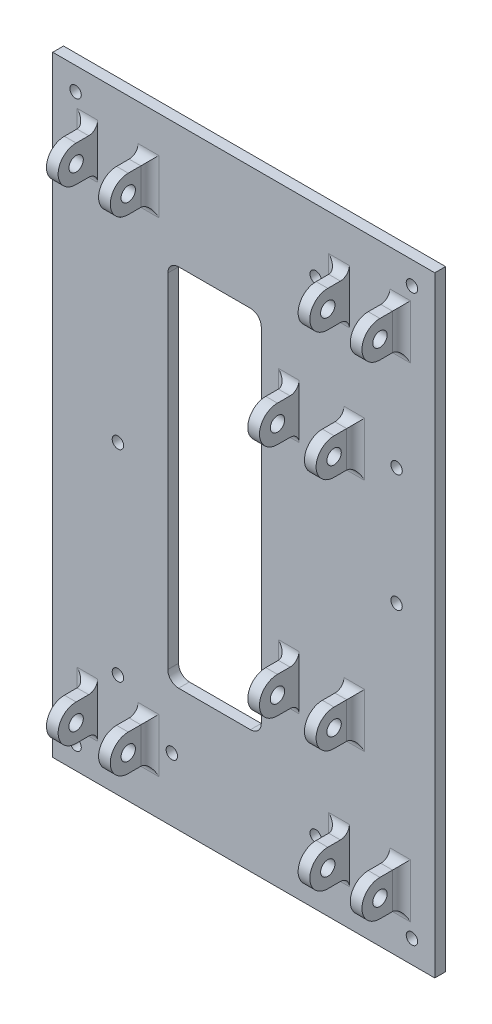
SolidWorks part; units mm, degrees
other "Markup3"
sketch "Sketch7" plane through (228.6, -342.9, 31.75) normal (0.076, -0.0024, 0.9971) x (0.9961, 0.0458, -0.0758)
other "Markup4"
sketch "Sketch8" plane through (228.6, -342.9, 31.75) normal (0.076, -0.0024, 0.9971) x (0.9961, 0.0458, -0.0758)
material "7075-T6 (SN)"
ref_plane "Front Plane" through (0, 0, 0) normal (0, 0, 1) x (1, 0, 0)
ref_plane "Top Plane" through (0, 0, 0) normal (0, 1, 0) x (1, 0, 0)
ref_plane "Right Plane" through (0, 0, 0) normal (1, 0, 0) x (0, 0, -1)
sketch "Sketch1" plane through (0, 0, 0) normal (0, 0, 1) x (1, 0, 0)
  line L1 (0, 0) -> (212.5, 0)
  line L2 (0, 0) -> (0, -339.725)
  line L3 (0, -339.725) -> (212.5, -339.725)
  line L4 (212.5, 0) -> (212.5, -339.725)
  dimension "D1" = 339.725
  dimension "D2" = 212.5
extrude "Boss-Extrude1" add sketch "Sketch1" along normal blind 6
sketch "Sketch2" plane through (0, 0, 6) normal (0, 0, 1) x (1, 0, 0)
  line L0 (0, 0) -> (0, -339.725) construction
  line L1 (25, -25.2425) -> (47.5, -25.2425) construction
  line L2 (25, -25.2425) -> (25, -45.2425)
  line L3 (25, -45.2425) -> (47.5, -45.2425) construction
  line L4 (47.5, -25.2425) -> (47.5, -45.2425)
  line L5 (165, -25.2425) -> (187.5, -25.2425) construction
  line L6 (165, -25.2425) -> (165, -45.2425)
  line L7 (165, -45.2425) -> (187.5, -45.2425) construction
  line L8 (187.5, -25.2425) -> (187.5, -45.2425)
  line L18 (137, -114.5325) -> (137, -225.1925) construction
  line L19 (0, -169.8625) -> (106.25, -169.8625) construction
  line L20 (54, -35.2425) -> (158.5, -35.2425) construction
  line L26 (165, -25.2425) -> (158.5, -25.2425)
  line L27 (165, -25.2425) -> (165, -45.2425)
  line L28 (165, -45.2425) -> (158.5, -45.2425)
  line L29 (158.5, -25.2425) -> (158.5, -45.2425)
  line L30 (187.5, -25.2425) -> (194, -25.2425)
  line L31 (187.5, -25.2425) -> (187.5, -45.2425)
  line L32 (187.5, -45.2425) -> (194, -45.2425)
  line L33 (194, -25.2425) -> (194, -45.2425)
  line L34 (47.5, -25.2425) -> (54, -25.2425)
  line L35 (47.5, -25.2425) -> (47.5, -45.2425)
  line L36 (47.5, -45.2425) -> (54, -45.2425)
  line L37 (54, -25.2425) -> (54, -45.2425)
  line L38 (25, -25.2425) -> (18.5, -25.2425)
  line L39 (25, -25.2425) -> (25, -45.2425)
  line L40 (25, -45.2425) -> (18.5, -45.2425)
  line L41 (18.5, -25.2425) -> (18.5, -45.2425)
  line L65 (212.5, -339.725) -> (212.5, 0) construction
  line L66 (137, -225.1925) -> (162, -225.1925) construction
  line L67 (158.5, -304.4825) -> (194, -304.4825) construction
  line L68 (149.5, -104.5325) -> (149.5, -235.1925) construction
  line L76 (18.5, -35.2425) -> (54, -35.2425) construction
  line L77 (18.5, -304.4825) -> (54, -304.4825) construction
  line L78 (36.25, -35.2425) -> (36.25, -304.4825) construction
  line L79 (137, -94.5325) -> (162, -94.5325) construction
  line L80 (54, -304.4825) -> (158.5, -304.4825) construction
  line L81 (106.25, -35.2425) -> (106.25, -304.4825) construction
  line L82 (106.25, -169.8625) -> (212.5, -169.8625) construction
  line L83 (130.5, -94.5325) -> (130.5, -114.5325)
  line L84 (137, -114.5325) -> (130.5, -114.5325)
  line L86 (137, -94.5325) -> (130.5, -94.5325)
  line L88 (137, -94.5325) -> (137, -114.5325)
  line L89 (162, -114.5325) -> (168.5, -114.5325)
  line L90 (162, -114.5325) -> (162, -94.5325)
  line L91 (168.5, -94.5325) -> (168.5, -114.5325)
  line L92 (162, -94.5325) -> (168.5, -94.5325)
  line L93 (130.5, -235.1925) -> (168.5, -235.1925) construction
  line L96 (137, -245.1925) -> (162, -245.1925) construction
  line L97 (162, -245.1925) -> (168.5, -245.1925)
  line L98 (168.5, -245.1925) -> (168.5, -225.1925)
  line L103 (130.5, -104.5325) -> (168.5, -104.5325) construction
  line L104 (137, -114.5325) -> (162, -114.5325) construction
  line L106 (158.5, -35.2425) -> (194, -35.2425) construction
  line L108 (176.25, -35.2425) -> (176.25, -304.4825) construction
  line L109 (165, -294.4825) -> (187.5, -294.4825) construction
  line L112 (165, -314.4825) -> (187.5, -314.4825) construction
  line L113 (25, -294.4825) -> (47.5, -294.4825) construction
  line L114 (25, -314.4825) -> (47.5, -314.4825) construction
  line L117 (162, -114.5325) -> (162, -225.1925) construction
  line L118 (18.5, -314.4825) -> (18.5, -294.4825)
  line L119 (25, -294.4825) -> (18.5, -294.4825)
  line L120 (25, -314.4825) -> (25, -294.4825)
  line L121 (25, -314.4825) -> (18.5, -314.4825)
  line L122 (54, -314.4825) -> (54, -294.4825)
  line L123 (47.5, -294.4825) -> (54, -294.4825)
  line L124 (47.5, -314.4825) -> (47.5, -294.4825)
  line L125 (47.5, -314.4825) -> (54, -314.4825)
  line L126 (194, -314.4825) -> (194, -294.4825)
  line L127 (187.5, -294.4825) -> (194, -294.4825)
  line L128 (187.5, -314.4825) -> (187.5, -294.4825)
  line L129 (187.5, -314.4825) -> (194, -314.4825)
  line L130 (158.5, -314.4825) -> (158.5, -294.4825)
  line L131 (165, -294.4825) -> (158.5, -294.4825)
  line L132 (165, -314.4825) -> (165, -294.4825)
  line L133 (165, -314.4825) -> (158.5, -314.4825)
  line L134 (187.5, -314.4825) -> (187.5, -294.4825)
  line L135 (165, -314.4825) -> (165, -294.4825)
  line L136 (47.5, -314.4825) -> (47.5, -294.4825)
  line L137 (25, -314.4825) -> (25, -294.4825)
  line L138 (162, -225.1925) -> (162, -245.1925)
  line L139 (162, -225.1925) -> (168.5, -225.1925)
  line L140 (137, -245.1925) -> (137, -225.1925)
  line L141 (137, -245.1925) -> (130.5, -245.1925)
  line L142 (137, -225.1925) -> (130.5, -225.1925)
  line L143 (130.5, -245.1925) -> (130.5, -225.1925)
  point P63 (194, -35.2425)
  point P101 (212.5, -169.8625)
  point P103 (158.5, -35.2425)
  dimension "D5" = 43.25
  dimension "D1" = 20
  dimension "D2" = 22.5
  dimension "D3" = 6.5
  dimension "D4" = 199.95
  dimension "D6" = 134.62
  dimension "D7" = 134.62
  dimension "D8" = 25
  dimension "D9" = 70
  dimension "D10" = 25
extrude "Boss-Extrude2" add sketch "Sketch2" along normal blind 24 contours L133 L132 L131 L130 | L128 L129 L126 L127 | L139 L138 L97 L98 | L143 L141 L140 L142 | L124 L125 L122 L123 | L121 L120 L119 L118 | L92 L90 L89 L91 | L88 L86 L83 L84 | L33 L30 L8 L32 | L37 L34 L4 L36 | L38 L41 L40 L2 | L26 L29 L28 L27 region at (21.75, -35.2425, 6) region at (50.75, -35.2425, 6) region at (190.75, -35.2425, 6) region at (133.75, -104.5325, 6) region at (165.25, -104.5325, 6) region at (165.25, -235.1925, 6) region at (21.75, -304.4825, 6) region at (50.75, -304.4825, 6) region at (190.75, -304.4825, 6) region at (161.75, -304.4825, 6) region at (133.75, -235.1925, 6)
sketch "Sketch3" plane through (18.5, 0, 0) normal (-1, 0, 0) x (0, 0, 1)
  line L0 (18, -104.5325) -> (6, -104.5325) construction
  line L1 (18, -304.4825) -> (6, -304.4825) construction
  line L2 (22, -235.1925) -> (37.7332, -235.1925) construction
  line L3 (22, -235.1925) -> (6, -235.1925) construction
  line L4 (18, -35.2425) -> (6, -35.2425) construction
  line L5 (6, -25.2425) -> (6, -45.2425) construction
  line L6 (6, -245.1925) -> (6, -225.1925) construction
  line L7 (6, 0) -> (6, -339.725) construction
  line L9 (18, -25.2425) -> (18, -12.9829)
  line L10 (18, -12.9829) -> (51.9495, -12.9829)
  line L11 (6, -245.1925) -> (6, -225.1925) construction
  line L12 (51.9495, -12.9829) -> (51.9495, -57.481)
  line L13 (51.9495, -57.481) -> (18, -57.481)
  line L14 (18, -57.481) -> (18, -45.2425)
  line L15 (52.4423, -132.3991) -> (18, -132.3991)
  line L16 (18, -94.5325) -> (18, -71.5915)
  line L17 (18, -71.5915) -> (52.4423, -71.5915)
  line L18 (18, -132.3991) -> (18, -114.5325)
  line L19 (52.4423, -71.5915) -> (52.4423, -132.3991)
  line L20 (52.5995, -270.3754) -> (18, -270.3754)
  line L21 (18, -225.1925) -> (18, -207.3064)
  line L22 (18, -207.3064) -> (52.5995, -207.3064)
  line L23 (18, -270.3754) -> (18, -245.1925)
  line L24 (52.5995, -207.3064) -> (52.5995, -270.3754)
  line L25 (52.621, -326.7211) -> (18, -326.7211)
  line L26 (18, -294.4825) -> (18, -282.2228)
  line L27 (18, -282.2228) -> (52.621, -282.2228)
  line L28 (18, -326.7211) -> (18, -314.4825)
  line L29 (52.621, -282.2228) -> (52.621, -326.7211)
  line L30 (6, -94.5325) -> (6, -114.5325) construction
  line L31 (30, -25.2425) -> (6, -25.2425) construction
  line L32 (30, -94.5325) -> (6, -94.5325) construction
  line L35 (6, -314.4825) -> (6, -294.4825) construction
  line L36 (6, -314.4825) -> (6, -294.4825) construction
  line L37 (18, -35.2425) -> (18, -104.5325) construction
  line L38 (18, -104.5325) -> (18, -235.1925) construction
  line L39 (18, -235.1925) -> (18, -304.4825) construction
  line L41 (30, -225.1925) -> (6, -225.1925) construction
  circle A0 centre (18, -35.2425) radius 4
  circle A1 centre (18, -235.1925) radius 4
  circle A2 centre (18, -35.2425) radius 5.5 construction
  circle A3 centre (18, -304.4825) radius 4
  circle A4 centre (18, -104.5325) radius 4
  arc A5 (18, -45.2425) -> (18, -25.2425) centre (18, -35.2425) ccw
  arc A6 (18, -114.5325) -> (18, -94.5325) centre (18, -104.5325) ccw
  arc A7 (18, -245.1925) -> (18, -225.1925) centre (18, -235.1925) ccw
  arc A8 (18, -314.4825) -> (18, -294.4825) centre (18, -304.4825) ccw
  point P62 (6, -304.4825)
  point P67 (6, -235.1925)
  dimension "D1" = 8
  dimension "D2" = 8
  dimension "D4" = 11
  dimension "D3" = 12
extrude "Cut-Extrude1" cut sketch "Sketch3" against normal through all both and the other way through all
fillet "Fillet2" radius 5 36 edges at (158.5, -304.4825, 6) (18.5, -304.4825, 6) (21.75, -45.2425, 6) (18.5, -35.2425, 6) (21.75, -25.2425, 6) (50.75, -25.2425, 6) (50.75, -45.2425, 6) (54, -35.2425, 6) (161.75, -25.2425, 6) (190.75, -25.2425, 6) (194, -35.2425, 6) (190.75, -45.2425, 6) (161.75, -45.2425, 6) (158.5, -35.2425, 6) (168.5, -104.5325, 6) (165.25, -114.5325, 6) (133.75, -114.5325, 6) (130.5, -104.5325, 6) (165.25, -94.5325, 6) (133.75, -94.5325, 6) (21.75, -294.4825, 6) (50.75, -294.4825, 6) (54, -304.4825, 6) (194, -304.4825, 6) (161.75, -294.4825, 6) (190.75, -294.4825, 6) (190.75, -314.4825, 6) (161.75, -314.4825, 6) (50.75, -314.4825, 6) (21.75, -314.4825, 6) (165.25, -225.1925, 6) (133.75, -225.1925, 6) (130.5, -235.1925, 6) (133.75, -245.1925, 6) (165.25, -245.1925, 6) (168.5, -235.1925, 6)
sketch "Sketch5" plane through (0, 0, 6) normal (0, 0, 1) x (1, 0, 0)
  line L0 (212.5, 0) -> (0, 0) construction
  line L1 (0, 0) -> (0, -339.725) construction
  line L2 (212.5, -339.725) -> (212.5, 0) construction
  line L5 (0, -169.8625) -> (212.5, -169.8625) construction
  line L6 (153.5, -35.2425) -> (59, -35.2425) construction
  line L7 (59, -20.2425) -> (59, -50.2425) construction
  line L8 (191.25, -104.5325) -> (191.25, -169.8625) construction
  line L9 (13.5, -50.2425) -> (59, -50.2425) construction
  line L10 (25, -50.2425) -> (13.5, -50.2425) construction
  line L11 (36.25, -50.2425) -> (36.25, -169.8625) construction
  line L15 (173.5, -89.5325) -> (173.5, -119.5325) construction
  line L16 (106.25, 0) -> (106.25, -339.725) construction
  line L17 (173.5, -104.5325) -> (191.25, -104.5325) construction
  line L26 (0, -339.725) -> (212.5, -339.725) construction
  circle A0 centre (12.7, -12.7) radius 3.175
  circle A1 centre (199.8, -12.7) radius 3.175
  circle A2 centre (66.25, -35.2425) radius 3.175
  circle A3 centre (146.25, -35.2425) radius 3.175
  circle A4 centre (176.25, -57.8625) radius 3.175
  circle A5 centre (36.25, -57.8625) radius 3.175
  circle A6 centre (191.25, -104.5325) radius 3.175
  circle A7 centre (36.25, -169.8625) radius 3.175
  circle A8 centre (191.25, -169.8625) radius 3.175
  circle A9 centre (36.25, -281.8625) radius 3.175
  circle A10 centre (66.25, -304.4825) radius 3.175
  circle A11 centre (12.7, -327.025) radius 3.175
  circle A12 centre (199.8, -327.025) radius 3.175
  circle A13 centre (146.25, -304.4825) radius 3.175
  circle A15 centre (191.25, -235.1925) radius 3.175
  dimension "D1" = 93.55
  dimension "D3" = 40
  dimension "D5" = 85
  dimension "D8" = 6.35
  dimension "D2" = 157.1625
  dimension "D4" = 112
extrude "Cut-Extrude2" cut sketch "Sketch5" against normal through all contours A0 | A5 | A3 | A1 | A4 | A6 | A7 | A8 | A12 | A13 | A10 | A9 | A11 region at (12.7, -12.7, 6) region at (199.8, -12.7, 6) region at (146.25, -35.2425, 6) region at (176.25, -57.8625, 6) region at (36.25, -57.8625, 6) region at (191.25, -104.5325, 6) region at (36.25, -169.8625, 6) region at (191.25, -169.8625, 6) region at (36.25, -281.8625, 6) region at (66.25, -304.4825, 6) region at (12.7, -327.025, 6) region at (199.8, -327.025, 6) region at (146.25, -304.4825, 6)
sketch "Sketch9" plane through (0, 0, 6) normal (0, 0, 1) x (1, 0, 0)
  line L0 (0, -169.8625) -> (212.5, -169.8625) construction
  line L11 (0, 0) -> (0, -339.725) construction
  line L12 (212.5, -339.725) -> (212.5, 0) construction
  line L14 (70, -271.3625) -> (110, -271.3625)
  line L15 (64, -265.3625) -> (64, -74.3625)
  line L16 (70, -68.3625) -> (110, -68.3625)
  line L17 (116, -265.3625) -> (116, -74.3625)
  line L18 (64, -271.3625) -> (116, -68.3625) construction
  line L19 (64, -68.3625) -> (116, -271.3625) construction
  arc A0 (110, -271.3625) -> (116, -265.3625) centre (110, -265.3625) ccw
  arc A1 (70, -271.3625) -> (64, -265.3625) centre (70, -265.3625) cw
  arc A2 (64, -74.3625) -> (70, -68.3625) centre (70, -74.3625) cw
  arc A5 (110, -68.3625) -> (116, -74.3625) centre (110, -74.3625) cw
  point P6 (90, -169.8625)
  point P22 (169.7848, -178.533)
  point P23 (214.9568, -251.8775)
  point P24 (158.9712, -185.193)
  point P25 (204.1432, -258.5375)
  dimension "D1" = 90
  dimension "D3" = 52
  dimension "D4" = 6
  dimension "D2" = 203
extrude "Cut-Extrude3" cut sketch "Sketch9" against normal through all contours L15 A2 L16 A5 L17 A0 L14 A1
sketch3d "3DSketch1"
  line L0 (18.5, -35.2425, 18) -> (194, -35.2425, 18) construction
  line L1 (25, -35.2425, 18) -> (18.5, -35.2425, 18) construction
  line L2 (194, -35.2425, 18) -> (187.5, -35.2425, 18) construction
  line L3 (194, -35.2425, 18) -> (187.5, -35.2425, 18) construction
  line L5 (194, -304.4825, 18) -> (187.5, -304.4825, 18) construction
  line L6 (194, -304.4825, 18) -> (18.5, -304.4825, 18) construction
  line L7 (25, -304.4825, 18) -> (18.5, -304.4825, 18) construction
  circle A0 centre (194, -35.2425, 18) radius 4 construction
  point P17 (198, -35.2425, 18)
  point P18 (194, -35.2425, 18)
